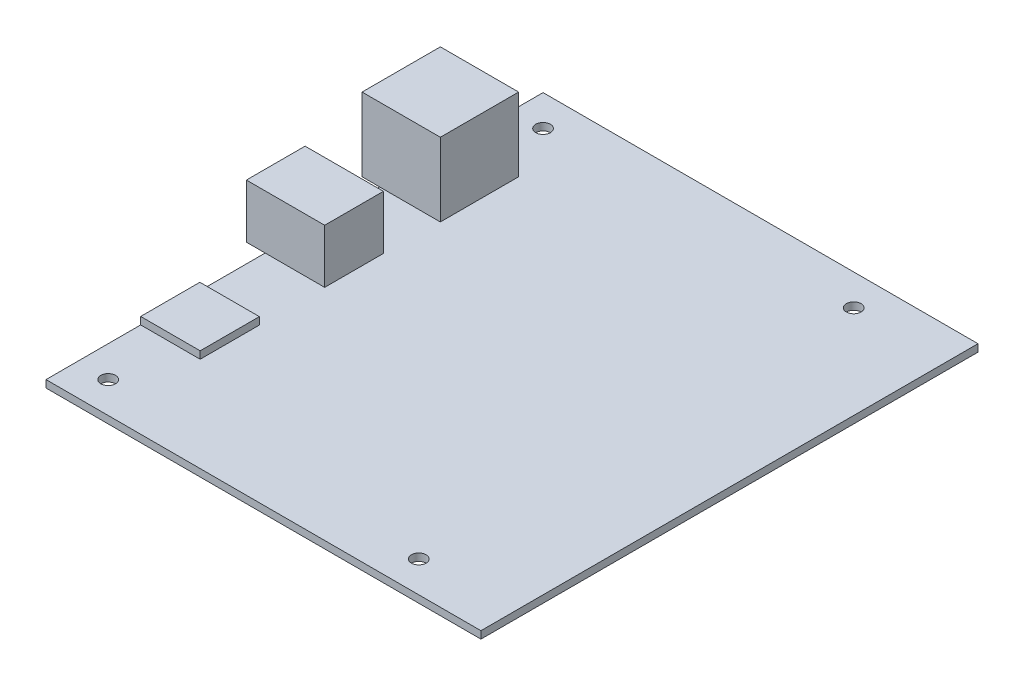
SolidWorks part; units mm, degrees
ref_plane "Front Plane" through (0, 0, 0) normal (0, 0, 1) x (1, 0, 0)
ref_plane "Top Plane" through (0, 0, 0) normal (0, 1, 0) x (1, 0, 0)
ref_plane "Right Plane" through (0, 0, 0) normal (1, 0, 0) x (0, 0, -1)
sketch "Sketch1" plane through (0, 0, 0) normal (0, 1, 0) x (1, 0, 0)
  line L0 (0, 0) -> (0, 86.3847) construction
  line L1 (0, 0) -> (-141.2858, 0) construction
  line L3 (-44.45, 50.8) -> (44.45, 50.8)
  line L4 (-44.45, 50.8) -> (-44.45, -50.8)
  line L5 (-44.45, -50.8) -> (44.45, -50.8)
  line L6 (44.45, 50.8) -> (44.45, -50.8)
  circle A0 centre (-38.1, 44.45) radius 1.5
  circle A1 centre (25.4, 44.45) radius 1.5
  circle A2 centre (-38.1, 44.45) radius 1.5
  circle A3 centre (-38.1, -44.45) radius 1.5
  circle A4 centre (25.4, -44.45) radius 1.5
  dimension "D3" = 3
  dimension "D1" = 101.6
  dimension "D2" = 88.9
  dimension "D4" = 88.9
  dimension "D5" = 6.35
  dimension "D6" = 63.5
extrude "Boss-Extrude1" add sketch "Sketch1" along normal blind 1.5 contours L6 L3 L4 L5 A4 A3 A1 A0 region at (0.0199, 0, 0)
sketch "Sketch3" plane through (0, 1.5, 0) normal (0, 1, 0) x (1, 0, 0)
  line L0 (-44.45, 50.8) -> (-44.45, -50.8) construction
  line L1 (-48.044, 33.4) -> (-32.044, 33.4)
  line L2 (-48.044, 33.4) -> (-48.044, 17.4)
  line L3 (-48.044, 17.4) -> (-32.044, 17.4)
  line L4 (-32.044, 33.4) -> (-32.044, 17.4)
  line L5 (-48.29, 6) -> (-32.29, 6)
  line L6 (-48.29, 6) -> (-48.29, -6)
  line L7 (-48.29, -6) -> (-32.29, -6)
  line L8 (-32.29, 6) -> (-32.29, -6)
  line L9 (-44.45, -19.35) -> (-32.29, -19.35)
  line L10 (-44.45, -19.35) -> (-44.45, -31.45)
  line L11 (-44.45, -31.45) -> (-32.29, -31.45)
  line L12 (-32.29, -19.35) -> (-32.29, -31.45)
  line L13 (-48.044, 25.4) -> (-32.044, 25.4) construction
  line L14 (-48.29, 0) -> (-32.29, 0) construction
  line L16 (-44.45, -25.4) -> (-32.29, -25.4) construction
  line L18 (-44.45, -50.8) -> (44.45, -50.8) construction
  line M7 (-44.45, 50.8) -> (-44.45, -50.8)
  dimension "D2" = 25.4
  dimension "D3" = 50.8
  dimension "D4" = 12.1
  dimension "D5" = 12
  dimension "D6" = 16
  dimension "D7" = 3.594
  dimension "D8" = 3.84
  dimension "D9" = 16
  dimension "D10" = 16
  dimension "D11" = 76.2
extrude "Boss-Extrude2" add sketch "Sketch3" along normal blind 15 contours L4 L1 L3 M7 | L2 L3 L1 M7 region at (-46.247, 1.5, -25.4) region at (-38.247, 1.5, -25.4)
extrude "Boss-Extrude3" add sketch "Sketch3<3>" along normal blind 11 contours L8 L5 L7 M7 | L6 L7 L5 M7 region at (-38.37, 1.5, 0) region at (-46.37, 1.5, 0)
sketch "Sketch3<3>" plane through (0, 1.5, 0) normal (0, 1, 0) x (1, 0, 0) same geometry as "Sketch3"
extrude "Boss-Extrude4" add sketch "Sketch3<4>" along normal blind 1.5 contours L12 L9 L11 M7 region at (-38.37, 1.5, 25.4)
sketch "Sketch3<4>" plane through (0, 1.5, 0) normal (0, 1, 0) x (1, 0, 0) same geometry as "Sketch3"
